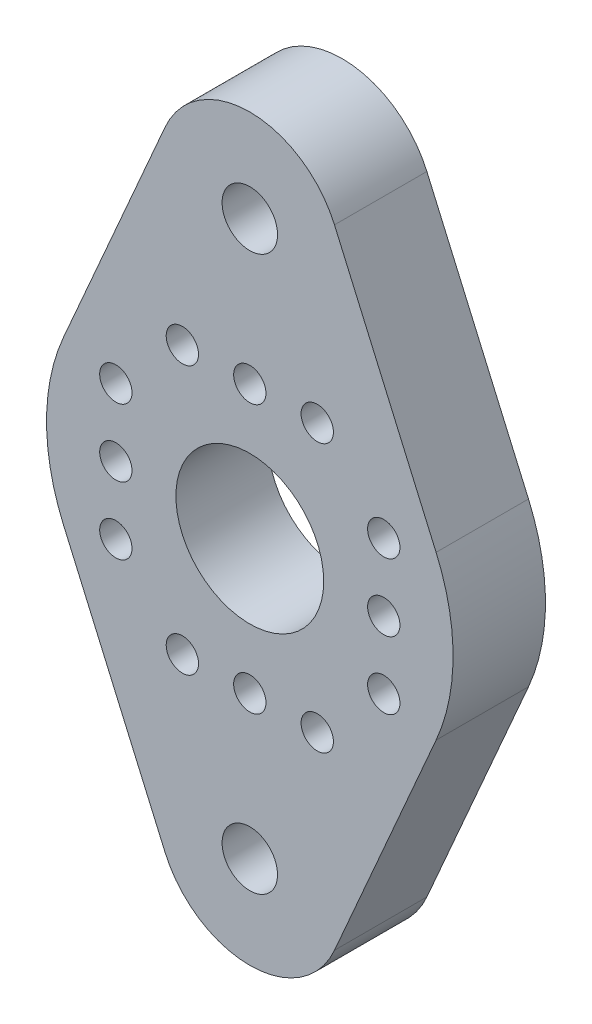
SolidWorks part; units mm, degrees
ref_plane "Plan de face" through (0, 0, 0) normal (0, 0, 1) x (1, 0, 0)
ref_plane "Plan de dessus" through (0, 0, 0) normal (0, 1, 0) x (1, 0, 0)
ref_plane "Plan de droite" through (0, 0, 0) normal (1, 0, 0) x (0, 0, -1)
sketch "Esquisse1" plane through (0, 0, 0) normal (0, 0, 1) x (1, 0, 0)
  line L0 (0, 0) -> (7.25, 0) construction
  line L1 (7.25, 3.65) -> (7.25, 0) construction
  line L2 (0, 0) -> (7.25, 0) construction
  line L3 (0, 0) -> (0, 15) construction
  line L4 (-10.0817, 4.4) -> (-4.5826, 17)
  line L5 (4.5826, 17) -> (10.0817, 4.4)
  line L6 (0, 0) -> (-11, 0) construction
  line L7 (4.5826, -17) -> (10.0817, -4.4)
  line L8 (-10.0817, -4.4) -> (-4.5826, -17)
  circle A0 centre (0, 0) radius 10.5 construction
  circle A1 centre (0, 0) radius 4
  circle A2 centre (7.25, 0) radius 0.875
  circle A3 centre (7.25, 3.65) radius 0.875
  circle A4 centre (7.25, -3.65) radius 0.875
  circle A5 centre (3.65, -7.25) radius 0.875
  circle A6 centre (0, -7.25) radius 0.875
  circle A7 centre (-3.65, -7.25) radius 0.875
  circle A8 centre (-7.25, -3.65) radius 0.875
  circle A9 centre (-7.25, 0) radius 0.875
  circle A10 centre (-7.25, 3.65) radius 0.875
  circle A11 centre (-3.65, 7.25) radius 0.875
  circle A12 centre (0, 7.25) radius 0.875
  circle A13 centre (3.65, 7.25) radius 0.875
  circle A14 centre (0, 15) radius 1.5
  arc A15 (-4.5826, 17) -> (4.5826, 17) centre (0, 15) cw
  arc A16 (-10.0817, -4.4) -> (-10.0817, 4.4) centre (0, 0) cw
  arc A17 (10.0817, -4.4) -> (10.0817, 4.4) centre (0, 0) ccw
  circle A18 centre (0, -15) radius 1.5
  arc A19 (-4.5826, -17) -> (4.5826, -17) centre (0, -15) ccw
  dimension "D1" = 21
  dimension "D2" = 8
  dimension "D5" = 1.75
  dimension "D8" = 5
  dimension "D9" = 11
  dimension "D10" = 3
  dimension "D3" = 7.25
  dimension "D4" = 3.65
  dimension "D7" = 15
  dimension "D6" = 4
extrude "Boss.-Extru.1" add sketch "Esquisse1" along normal blind 5
